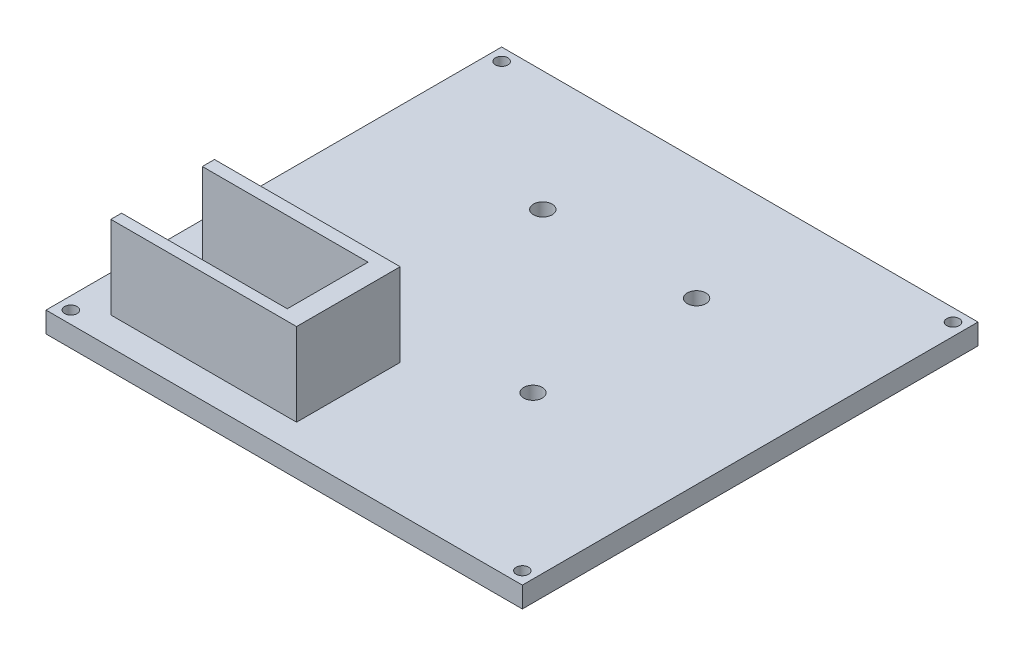
SolidWorks part; units mm, degrees
ref_plane "Front Plane" through (0, 0, 0) normal (0, 0, 1) x (1, 0, 0)
ref_plane "Top Plane" through (0, 0, 0) normal (0, 1, 0) x (1, 0, 0)
ref_plane "Right Plane" through (0, 0, 0) normal (1, 0, 0) x (0, 0, -1)
sketch "Sketch1" plane through (0, 0, 0) normal (0, 1, 0) x (1, 0, 0)
  line L1 (-65.8166, 36.4271) -> (49.1834, 36.4271)
  line L2 (-65.8166, 36.4271) -> (-65.8166, -73.5729)
  line L3 (-65.8166, -73.5729) -> (49.1834, -73.5729)
  line L4 (49.1834, 36.4271) -> (49.1834, -73.5729)
  circle A0 centre (-62.8166, 33.4271) radius 1.5
  circle A1 centre (46.1834, 33.3941) radius 1.5
  circle A2 centre (-62.8166, -70.5729) radius 1.5
  circle A3 centre (46.1834, -70.5729) radius 1.5
  point P8 (-62.8166, -70.5729)
  point P11 (46.1834, -70.5729)
  dimension "D3" = 3
  dimension "D4" = 3
  dimension "D5" = 3
  dimension "D6" = 3
  dimension "D7" = 3
  dimension "D8" = 3
  dimension "D9" = 3
  dimension "D10" = 3
  dimension "D1" = 115
  dimension "D2" = 110
extrude "Boss-Extrude1" add sketch "Sketch1" along normal blind 5
sketch "Sketch4" plane through (0, 5, 0) normal (0, 1, 0) x (1, 0, 0)
  line L0 (-8.3166, 36.4271) -> (-8.3166, -73.5729) construction
  line L1 (49.1834, 36.4271) -> (-65.8166, 36.4271) construction
  line L2 (-65.8166, -73.5729) -> (49.1834, -73.5729) construction
  line L3 (-65.8166, -18.5729) -> (49.1834, -18.5729) construction
  line L4 (-65.8166, 36.4271) -> (-65.8166, -73.5729) construction
  line L5 (49.1834, -73.5729) -> (49.1834, 36.4271) construction
  line L7 (-32.3166, -39.5729) -> (15.6834, -39.5729)
  line L8 (-32.3166, -39.5729) -> (-32.3166, 13.4271)
  line L9 (-32.3166, 13.4271) -> (15.6834, 13.4271)
  line L10 (15.6834, -39.5729) -> (15.6834, 13.4271)
  line L11 (-32.3166, -39.5729) -> (15.6834, 13.4271) construction
  line L12 (-32.3166, 13.4271) -> (15.6834, -39.5729) construction
  line L25 (-56.9618, -64.1817) -> (-16.9618, -64.1817)
  line L26 (-56.9618, -64.1817) -> (-56.9618, -44.6817)
  line L27 (-56.9618, -44.6817) -> (-16.9618, -44.6817)
  line L28 (-16.9618, -64.1817) -> (-16.9618, -44.6817)
  line L29 (-56.9618, -64.1817) -> (-16.9618, -64.1817)
  line L30 (-56.9618, -64.1817) -> (-56.9618, -66.7755)
  line L31 (-56.9618, -66.7755) -> (-16.9618, -66.7755)
  line L32 (-16.9618, -64.1817) -> (-16.9618, -66.7755)
  line L33 (-56.9618, -44.6817) -> (-16.9618, -44.6817)
  line L34 (-56.9618, -44.6817) -> (-56.9618, -41.7535)
  line L35 (-56.9618, -41.7535) -> (-16.9618, -41.7535)
  line L36 (-16.9618, -44.6817) -> (-16.9618, -41.7535)
  line L37 (-16.9618, -41.7535) -> (-12.1251, -41.7535)
  line L38 (-16.9618, -41.7535) -> (-16.9618, -66.7755)
  line L39 (-16.9618, -66.7755) -> (-12.1251, -66.7755)
  line L40 (-12.1251, -41.7535) -> (-12.1251, -66.7755)
  circle A0 centre (-26.8826, -32.0729) radius 2.25
  circle A1 centre (10.2534, 7.4271) radius 2.25
  circle A2 centre (-26.8826, 7.4271) radius 2.25
  circle A3 centre (10.2534, -32.0729) radius 2.25
  point P12 (-8.3166, -13.0729)
  point P17 (10.2534, -32.0936)
  point P18 (-26.8826, -32.0936)
  dimension "D6" = 4.5
  dimension "D7" = 7.5
  dimension "D8" = 6
  dimension "D10" = 19.5
  dimension "D13" = 6
  dimension "D14" = 4.5
  dimension "D15" = 4.5
  dimension "D16" = 4.5
  dimension "D1" = 48
  dimension "D2" = 53
  dimension "D3" = 7.5
  dimension "D4" = 5.43
  dimension "D11" = 40
  dimension "D12" = 23
extrude "Boss-Extrude3" add sketch "Sketch4" along normal blind 20 contours L27 L36 L35 L34 | L40 L37 L36 L28 L32 L39 | L32 L25 L30 L31 region at (-36.9618, 5, 65.4786) region at (-14.5435, 5, 54.2645) region at (-36.9618, 5, 43.2176)
extrude "Cut-Extrude1" cut sketch "Sketch4<8>" against normal blind 5 contours A2 | A0 | A1 | A3
sketch "Sketch4<8>" plane through (0, 5, 0) normal (0, 1, 0) x (1, 0, 0) same geometry as "Sketch4"
